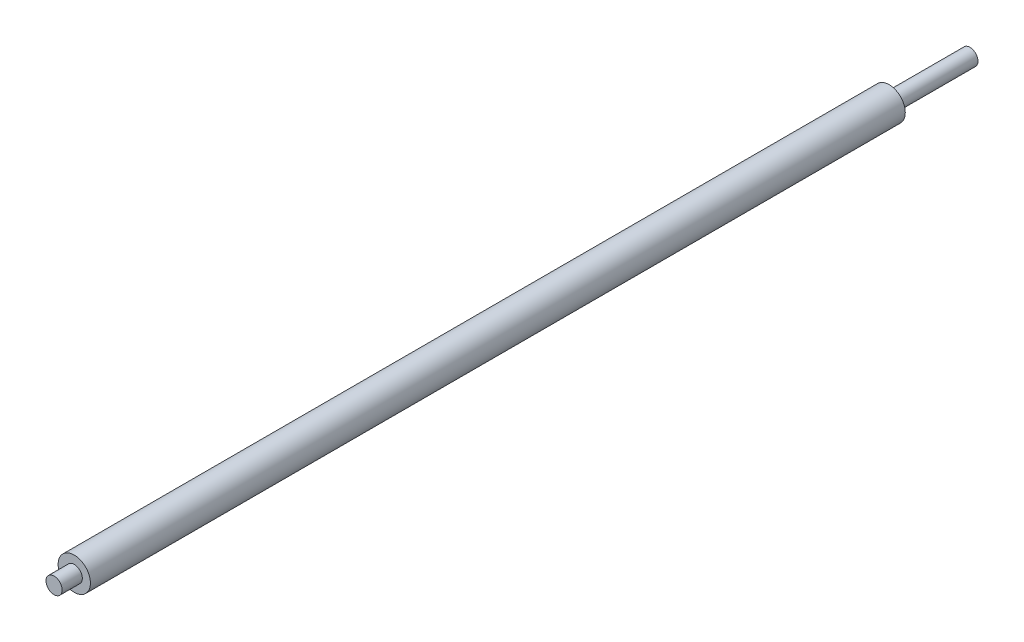
SolidWorks part; units mm, degrees
ref_plane "Front Plane" through (0, 0, 0) normal (0, 0, 1) x (1, 0, 0)
ref_plane "Top Plane" through (0, 0, 0) normal (0, 1, 0) x (1, 0, 0)
ref_plane "Right Plane" through (0, 0, 0) normal (1, 0, 0) x (0, 0, -1)
sketch "Sketch1" plane through (0, 0, 0) normal (0, 0, 1) x (1, 0, 0)
  circle A0 centre (0, 0) radius 6
  dimension "D1" = 12
extrude "Boss-Extrude1" add sketch "Sketch1" along normal mid plane 302.5
sketch "Sketch2" plane through (0, 0, 151.25) normal (0, 0, 1) x (1, 0, 0)
  circle A0 centre (0, 0) radius 3
  dimension "D1" = 6
extrude "Boss-Extrude2" add sketch "Sketch2" along normal blind 7.5
sketch "Sketch3" plane through (0, 0, -151.25) normal (0, 0, -1) x (-1, 0, 0)
  circle A0 centre (0, 0) radius 3
  dimension "D1" = 6
extrude "Boss-Extrude3" add sketch "Sketch3" along normal blind 30
